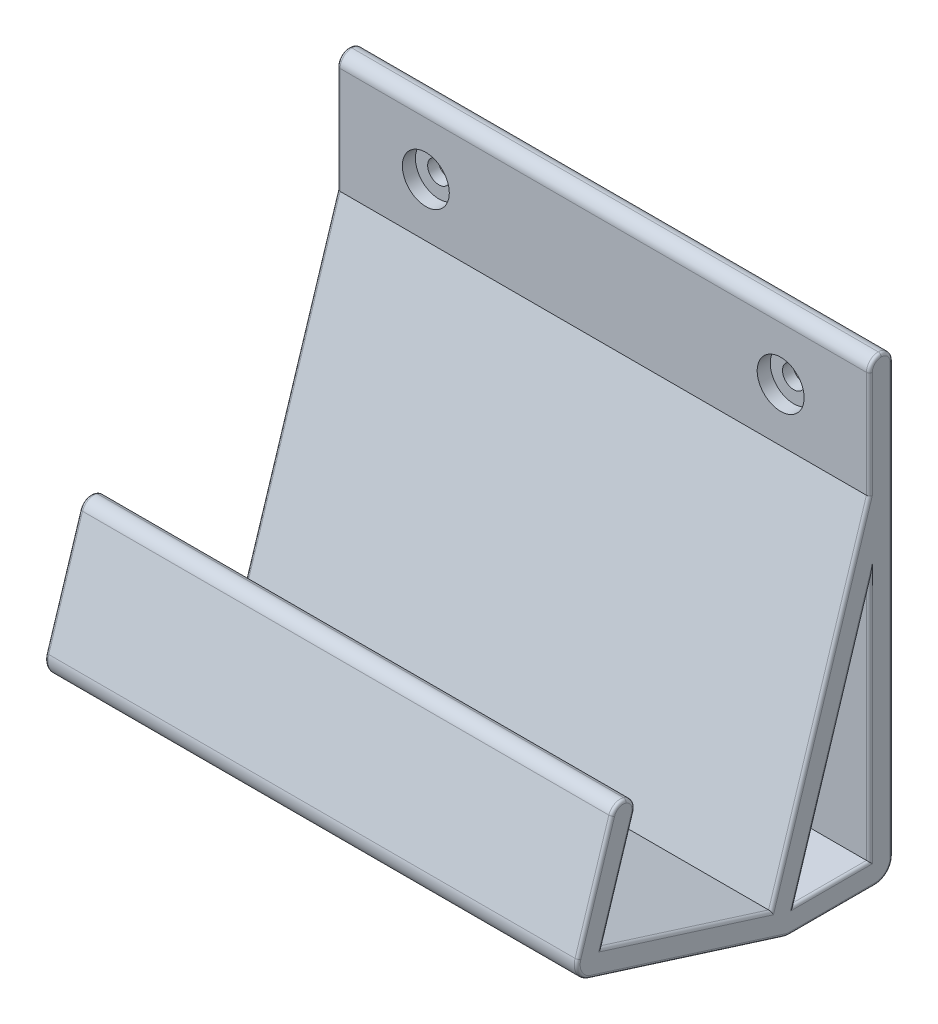
SolidWorks part; units mm, degrees
ref_plane "Front Plane" through (0, 0, 0) normal (0, 0, 1) x (1, 0, 0)
ref_plane "Top Plane" through (0, 0, 0) normal (0, 1, 0) x (1, 0, 0)
ref_plane "Right Plane" through (0, 0, 0) normal (1, 0, 0) x (0, 0, -1)
sketch "Sketch1" plane through (0, 0, 0) normal (1, 0, 0) x (0, 0, -1)
  line L0 (-22.5974, 28.0955) -> (-28.6115, 9.0212)
  line L1 (-28.6115, 9.0212) -> (0, 0)
  line L2 (0, 0) -> (16.5388, 52.4544)
  line L3 (16.5388, 52.4544) -> (26.5388, 52.4544)
  line L4 (26.5388, 52.4544) -> (55.4954, -3.1707)
  line L5 (21.5388, 52.4544) -> (21.5388, -28.1173) construction
  line L6 (-26.4123, 29.2983) -> (-33.6292, 6.4091)
  line L7 (-33.6292, 6.4091) -> (2.612, -5.0177)
  line L8 (2.612, -5.0177) -> (19.4717, 48.4544)
  line L9 (19.4717, 48.4544) -> (24.1116, 48.4544)
  line L10 (24.1116, 48.4544) -> (51.9474, -5.0177)
  line L11 (-26.4123, 29.2983) -> (-22.5974, 28.0955)
  line L12 (51.9474, -5.0177) -> (56.4569, -5.0177)
  line L13 (56.4569, -5.0177) -> (55.4954, -3.1707)
  dimension "D1" = 55
  dimension "D2" = 20
  dimension "D3" = 45
  dimension "D4" = 17.5
  dimension "D5" = 10
  dimension "D6" = 30
  dimension "D7" = 4
extrude "Boss-Extrude1" add sketch "Sketch1" along normal mid plane 90
sketch "Sketch2" plane through (45, 0, 0) normal (1, 0, 0) x (0, 0, -1)
  line L0 (16.5388, 52.4544) -> (16.5388, 39.1524)
  line L1 (2.612, -5.0177) -> (19.4717, 48.4544) construction
  line L2 (16.5388, 39.1524) -> (19.4717, 48.4544)
  line L3 (19.4717, 48.4544) -> (24.1116, 48.4544)
  line L4 (24.1116, 48.4544) -> (51.9474, -5.0177)
  line L5 (51.9474, -5.0177) -> (56.4569, -5.0177)
  line L6 (56.4569, -5.0177) -> (26.5388, 52.4544)
  line L7 (26.5388, 52.4544) -> (16.5388, 52.4544)
extrude "Cut-Extrude1" cut sketch "Sketch2" against normal through all
sketch "Sketch3" plane through (0, 0, -16.5388) normal (0, 0, -1) x (-1, 0, 0)
  line L0 (0, 52.4544) -> (0, -5.0177) construction
  line L1 (-45, 52.4544) -> (45, 52.4544) construction
  line L2 (-45, -5.0177) -> (45, -5.0177) construction
  line L4 (-45, 72.4544) -> (45, 72.4544)
  line L5 (-45, 72.4544) -> (-45, -25.0177)
  line L6 (-45, -25.0177) -> (45, -25.0177)
  line L7 (45, 72.4544) -> (45, -25.0177)
  line L8 (-45, 72.4544) -> (45, -25.0177) construction
  line L9 (-45, -25.0177) -> (45, 72.4544) construction
  line L10 (-45, -5.0177) -> (-45, 39.1524) construction
  point P6 (0, 23.7184)
  dimension "D1" = 20
extrude "Boss-Extrude2" add sketch "Sketch3" along normal blind 4
sketch "Sketch4" plane through (-45, 0, 0) normal (-1, 0, 0) x (0, 0, 1)
  line L1 (-2.612, -5.0177) -> (-20.5388, -5.0177)
  line L2 (-2.612, -5.0177) -> (-2.612, -25.0177)
  line L3 (-2.612, -25.0177) -> (-20.5388, -25.0177)
  line L4 (-20.5388, -5.0177) -> (-20.5388, -25.0177)
extrude "Cut-Extrude2" cut sketch "Sketch4" against normal through all
sketch "Sketch5" plane through (0, -5.0177, 0) normal (0, -1, 0) x (1, 0, 0)
  line L1 (-45, -2.612) -> (45, -2.612)
  line L2 (-45, -2.612) -> (-45, -20.5388)
  line L3 (-45, -20.5388) -> (45, -20.5388)
  line L4 (45, -2.612) -> (45, -20.5388)
extrude "Boss-Extrude3" add sketch "Sketch5" against normal blind 4
fillet "Fillet7" radius 3 3 edges at (0, -5.0177, -20.5388) (0, -5.0177, -2.612) (0, 6.4091, 33.6292)
fillet "Fillet8" radius 2 4 edges at (0, 72.4544, -16.5388) (0, 28.0955, 22.5974) (0, 72.4544, -20.5388) (0, 29.2983, 26.4123)
fillet "Fillet9" radius 0.5 36 edges at (-45, 26.2272, -8.2694) (-45, 4.5106, 14.3058) (-45, 17.6046, 25.9052) (-45, 27.713, 23.3322) (-45, 28.5635, 26.0297) (-45, 18.3306, 29.8704) (-45, 6.9829, 32.527) (-45, 0.3141, 14.2982) (-45, -4.9828, -2.6174) (-45, -5.0177, -10.3063) (-45, -4.139, -19.6601) (-45, 34.2184, -20.5388) (-45, 71.8686, -19.953) (-45, 71.8686, -17.1246) (-45, 61.4544, -16.5388) (-45, 19.0674, -16.5388) (-45, -1.0177, -10.206) (-45, 19.0674, -10.206) (45, 34.2184, -20.5388) (45, -4.139, -19.6601) (45, -5.0177, -10.3063) (45, -4.9828, -2.6174) (45, 0.3141, 14.2982) (45, 6.9829, 32.527) (45, 18.3306, 29.8704) (45, 28.5635, 26.0297) (45, 27.713, 23.3322) (45, 17.6046, 25.9052) (45, 4.5106, 14.3058) (45, 26.2272, -8.2694) (45, 61.4544, -16.5388) (45, 71.8686, -17.1246) (45, 71.8686, -19.953) (45, 19.0674, -16.5388) (45, 19.0674, -10.206) (45, -1.0177, -10.206)
hole_wizard "CBORE for #6 Binding Head Machine Screw1" positions "Sketch6" profile "Sketch7" counterbore size "#6" standard "ANSI Inch" end condition through all
sketch "Sketch6" plane through (0, 0, -16.5388) normal (0, 0, 1) x (1, 0, 0)
  line L0 (-45, 52.3775) -> (-45, 70.4544) construction
  line L1 (45, 70.4544) -> (45, 52.3775) construction
  line L2 (-44.5, 70.4544) -> (-44.5, 52.4544) construction
  point P0 (-30, 61.4544)
  point P2 (30, 61.4544)
  point P7 (-45, 61.416)
  point P12 (-44.5, 61.4544)
  dimension "D1" = 15
  dimension "D2" = 15
sketch "Sketch7" plane through (-30, 61.4544, -16.5388) normal (1, 0, 0) x (0, -1, 0)
  line L0 (0, 0) -> (0, 4)
  line L1 (0, 4) -> (1.8987, 4)
  line L3 (1.8987, 4) -> (1.8987, 2.2098)
  line L4 (1.8987, 2.2098) -> (3.9688, 2.2098)
  line L5 (3.9688, 2.2098) -> (3.9688, 0)
  line L7 (3.9688, 0) -> (0, 0)
  line L11 (0, -6.35) -> (0, 107.95) construction
  dimension "Thru Hole Dia." = 3.7973
  dimension "Thru Hole Depth" = 4
  dimension "C'Bore Dia." = 7.9375
  dimension "C'Bore Depth" = 2.2098
